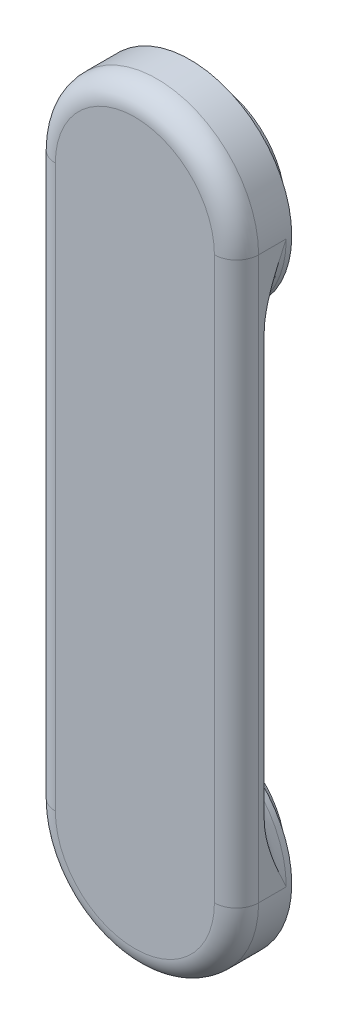
SolidWorks part; units mm, degrees
ref_plane "Front Plane" through (0, 0, 0) normal (0, 0, 1) x (1, 0, 0)
ref_plane "Top Plane" through (0, 0, 0) normal (0, 1, 0) x (1, 0, 0)
ref_plane "Right Plane" through (0, 0, 0) normal (1, 0, 0) x (0, 0, -1)
sketch "Sketch1" plane through (0, 0, 0) normal (0, 0, 1) x (1, 0, 0)
  line L0 (0, -31.75) -> (0, 31.75) construction
  line L1 (-11.5, -31.75) -> (-11.5, 31.75)
  line L2 (11.5, -31.75) -> (11.5, 31.75)
  arc A0 (-11.5, -31.75) -> (11.5, -31.75) centre (0, -31.75) ccw
  arc A1 (11.5, 31.75) -> (-11.5, 31.75) centre (0, 31.75) ccw
  circle A3 centre (0, -31.75) radius 11.5
  circle A4 centre (0, 31.75) radius 8.125
  circle A5 centre (0, -31.75) radius 8.125
  circle A6 centre (0, 31.75) radius 11.5
  point P2 (0, 0)
  dimension "D2" = 11.5
  dimension "D3" = 16.25
  dimension "D1" = 63.5
extrude "Boss-Extrude1" add sketch "Sketch1" along normal blind 3.125 contours L2 A1 L1 A0
extrude "Boss-Extrude2" add sketch "Sketch1<3>" against normal blind 3.125 contours A3 | A6
sketch "Sketch1<3>" plane through (0, 0, 0) normal (0, 0, 1) x (1, 0, 0) same geometry as "Sketch1"
extrude "Boss-Extrude3" add sketch "Sketch1<4>" against normal blind 5.75 contours A4 | A5
sketch "Sketch1<4>" plane through (0, 0, 0) normal (0, 0, 1) x (1, 0, 0) same geometry as "Sketch1"
sketch "Sketch2" plane through (0, 0, -5.75) normal (0, 0, -1) x (-1, 0, 0)
  circle A0 centre (0, 31.75) radius 7.5
  circle A1 centre (0, -31.75) radius 7.5
  dimension "D1" = 15
  dimension "D2" = 15
extrude "Cut-Extrude1" cut sketch "Sketch2" against normal blind 5.75
fillet "Fillet1" radius 2.5 8 edges at (0, -43.25, 3.125) (-11.5, 0, 3.125) (0, 43.25, 3.125) (8.125, -31.75, -3.125) (0, -20.25, 0) (0, 20.25, 0) (8.125, 31.75, -3.125) (11.5, 0, 3.125)
